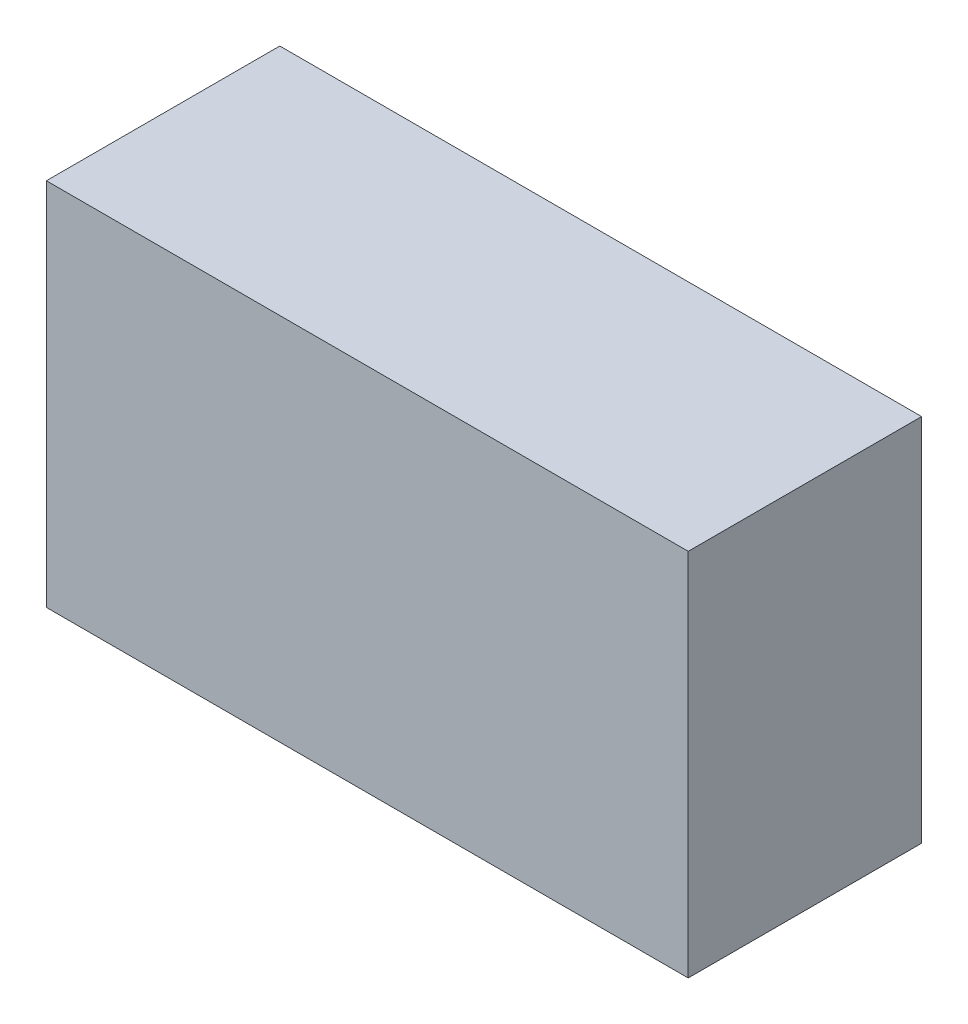
SolidWorks part; units mm, degrees
ref_plane "Front Plane" through (0, 0, 0) normal (0, 0, 1) x (1, 0, 0)
ref_plane "Top Plane" through (0, 0, 0) normal (0, 1, 0) x (1, 0, 0)
ref_plane "Right Plane" through (0, 0, 0) normal (1, 0, 0) x (0, 0, -1)
sketch "Sketch1" plane through (0, 0, 0) normal (0, 0, 1) x (1, 0, 0)
  line L0 (-419.1, 241.3) -> (419.1, -241.3) construction
  line L1 (-419.1, 241.3) -> (419.1, 241.3)
  line L2 (-419.1, 241.3) -> (-419.1, -241.3)
  line L3 (-419.1, -241.3) -> (419.1, -241.3)
  line L4 (419.1, 241.3) -> (419.1, -241.3)
  dimension "D1" = 838.2
  dimension "D2" = 482.6
extrude "Boss-Extrude1" add sketch "Sketch1" along normal mid plane 304.8
